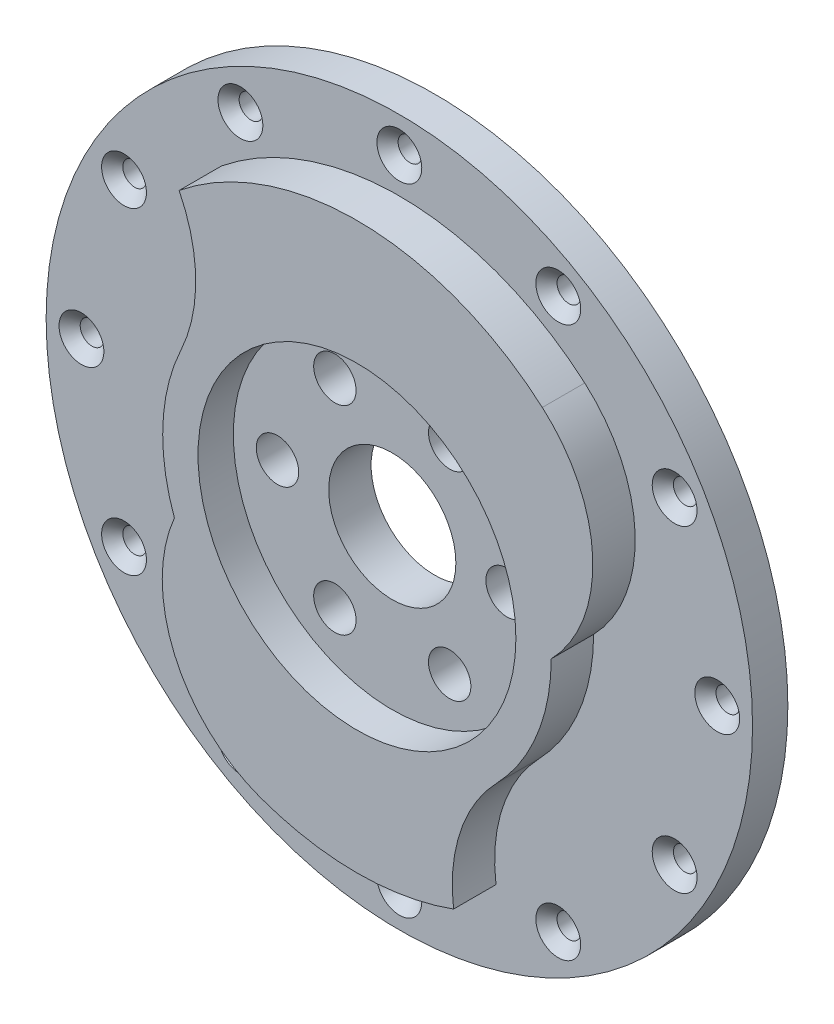
SolidWorks part; units mm, degrees
material "ASTM A36 Steel"
ref_plane "Front Plane" through (0, 0, 0) normal (0, 0, 1) x (1, 0, 0)
ref_plane "Top Plane" through (0, 0, 0) normal (0, 1, 0) x (1, 0, 0)
ref_plane "Right Plane" through (0, 0, 0) normal (1, 0, 0) x (0, 0, -1)
sketch "Sketch1" plane through (0, 0, 0) normal (0, 0, 1) x (1, 0, 0)
  circle A0 centre (0, 0) radius 100
  dimension "D1" = 200
extrude "Boss-Extrude1" add sketch "Sketch1" along normal blind 10
sketch "Sketch2" plane through (0, 0, 10) normal (0, 0, 1) x (1, 0, 0)
  line L0 (0, 0) -> (0, 141.6591) construction
  arc A0 (-50.3456, 62.1717) -> (52.4847, 60.3768) centre (0, 0) cw
  arc A1 (-27.3616, -75.1754) -> (27.3616, -75.1754) centre (0, 0) ccw
  arc A2 (-49.8469, 23.244) -> (-51.6831, -18.8111) centre (0, 0) ccw
  arc A3 (55, 0) -> (39.5637, -38.2062) centre (0, 0) cw
  arc A4 (-50.3456, 62.1717) -> (-49.8469, 23.244) centre (-90.4778, 42.1905) cw
  arc A5 (-51.6831, -18.8111) -> (-27.3616, -75.1754) centre (-12.9273, -35.5173) ccw
  arc A6 (27.3616, -75.1754) -> (39.5637, -38.2062) centre (71.8126, -69.3486) cw
  arc A7 (55, 0) -> (52.4847, 60.3768) centre (25.209, 28.9997) ccw
  circle A8 centre (0, 0) radius 45
  circle A9 centre (0, 0) radius 18
  dimension "D1" = 80
  dimension "D2" = 55
  dimension "D9" = 90
  dimension "D10" = 36
  dimension "D3" = 49
  dimension "D4" = 39
  dimension "D5" = 26
  dimension "D6" = 45
  dimension "D7" = 40
  dimension "D8" = 26
extrude "Boss-Extrude2" add sketch "Sketch2" along normal blind 12 contours A8 A0 A4 A2 A5 A1 A6 A3 A7 | A9 A8 | A9 region at (1.3611, 77.9766, 10) region at (-43.7272, 0, 10) region at (0, 0, 10)
extrude "Cut-Extrude1" cut sketch "Sketch2<4>" against normal blind 10 from surface contours A8 starting at face at (-0.4869, -6.5321, 22)
sketch "Sketch2<4>" plane through (0, 0, 10) normal (0, 0, 1) x (1, 0, 0) same geometry as "Sketch2"
extrude "Cut-Extrude2" cut sketch "Sketch2<5>" along normal through all both and the other way through all contours A9
sketch "Sketch2<5>" plane through (0, 0, 10) normal (0, 0, 1) x (1, 0, 0) same geometry as "Sketch2"
sketch "Sketch3" plane through (0, 0, 12) normal (0, 0, 1) x (1, 0, 0)
  circle A0 centre (32.5, 0) radius 6
  circle A1 centre (0, 0) radius 32.5 construction
  dimension "D1" = 12
  dimension "D2" = 65
extrude "Cut-Extrude3" cut sketch "Sketch3" against normal through all
pattern_circular "CirPattern1" count 6 over 360 about axis through (0, 0, 22) along (0, 0, 1) of "Cut-Extrude3"
sketch "Sketch5" plane through (0, 0, 0) normal (0, 1, 0) x (1, 0, 0)
  line L0 (90, 0) -> (90, -10) construction
  line L1 (100, 0) -> (-100, 0) construction
  line L2 (-100, -10) -> (100, -10) construction
  line L3 (83.65, -10) -> (86.65, -7)
  line L4 (86.65, -7) -> (86.65, 0)
  line L5 (90, 0) -> (90, -10)
  line L6 (83.65, -10) -> (90, -10)
  line L7 (86.65, 0) -> (90, 0)
  dimension "D1" = 45
  dimension "D2" = 6.7
  dimension "D3" = 7
  dimension "D4" = 90
revolve "Cut-Revolve2" cut sketch "Sketch5" angle 360 about L0
pattern_circular "CirPattern2" count 12 over 360 about axis through (0, 0, 10) along (0, 0, 1) of "Cut-Revolve2"
